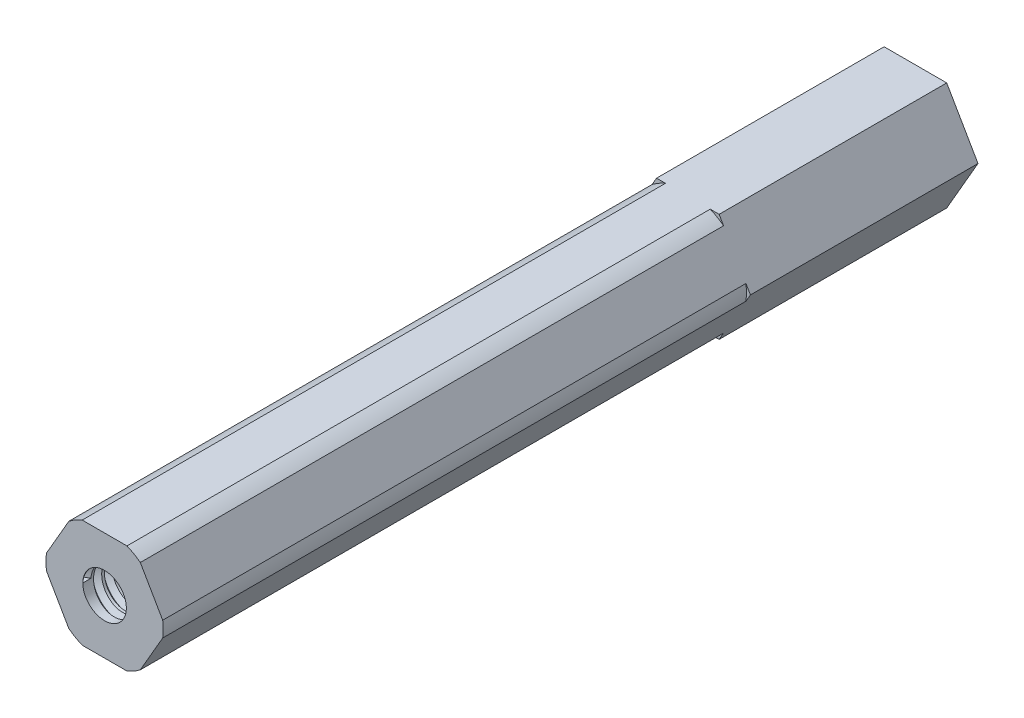
SolidWorks part; units mm, degrees
material "7075-T6 (SN)"
ref_plane "Alzado" through (0, 0, 0) normal (0, 0, 1) x (1, 0, 0)
ref_plane "Planta" through (0, 0, 0) normal (0, 1, 0) x (1, 0, 0)
ref_plane "Vista lateral" through (0, 0, 0) normal (1, 0, 0) x (0, 0, -1)
sketch "Croquis2" plane through (0, 0, 0) normal (0, 0, 1) x (1, 0, 0)
  line L1 (3.6662, -6.35) -> (7.3323, 0)
  line L2 (7.3323, 0) -> (3.6662, 6.35)
  line L3 (3.6662, 6.35) -> (-3.6662, 6.35)
  line L4 (-3.6662, 6.35) -> (-7.3323, 0)
  line L5 (-7.3323, 0) -> (-3.6662, -6.35)
  line L6 (-3.6662, -6.35) -> (3.6662, -6.35)
  circle A0 centre (0, 0) radius 6.35 construction
  dimension "D1" = 12.7
extrude "Extrusión Hex Profile" add sketch "Croquis2" along normal mid plane 95.0214
sketch "Croquis3" plane through (0, 0, 0) normal (0, 0, 1) x (1, 0, 0)
  circle A0 centre (0, 0) radius 2.5527
  dimension "D1" = 5.1054
extrude "Tap Hole 1" cut sketch "Croquis3" against normal blind 19.05 from surface starting at face at (0, 0, 47.5107)
extrude "Tap Hole 2" cut sketch "Croquis3<3>" along normal blind 19.05 from surface starting at face at (0, 0, -47.5107)
sketch "Croquis3<3>" plane through (0, 0, 0) normal (0, 0, 1) x (1, 0, 0) same geometry as "Croquis3"
sketch "Croquis7" plane through (0, 0, 0) normal (0, 0, 1) x (1, 0, 0)
  circle A0 centre (0, 0) radius 6.8707
  dimension "D1" = 13.7414
extrude "ThunderHex" cut sketch "Croquis7" along normal through all and the other way offset from surface 26.67 flip side to cut other way up to face at (2.5527, 0, -47.5107)
sketch "Croquis8" plane through (0, 0, 0) normal (0, 1, 0) x (1, 0, 0)
  line L0 (0, -47.5107) -> (-5.5562, -47.5107) construction
  line L1 (2.6237, -47.5107) -> (-2.6237, -47.5107) construction
  line L3 (0, -47.5107) -> (0, 0) construction
  line L4 (-5.5562, -47.5107) -> (-6.35, -46.717)
  line L5 (-6.35, -46.717) -> (-6.35, -45.9232)
  line L6 (-6.35, -45.9232) -> (-5.9055, -45.9232)
  line L7 (-5.9055, -45.9232) -> (-5.9055, -44.3357)
  line L8 (-5.9055, -44.3357) -> (-12.7, -44.3357)
  line L9 (-12.7, -44.3357) -> (-12.7, -47.5107)
  line L10 (-12.7, -47.5107) -> (-5.5562, -47.5107)
  line L11 (-4.1874, -47.5107) -> (-6.8111, -47.5107) construction
  dimension "D1" = 11.811
  dimension "D2" = 12.7
  dimension "D3" = 45
  dimension "D4" = 0.7937
  dimension "D6" = 0.7937
  dimension "D7" = 3.175
  dimension "D8" = 25.4
revolve "Retaining Ring 1" [suppressed] cut sketch "Croquis8" angle 360 about L3
sketch "Croquis9" plane through (0, 0, 0) normal (0, -1, 0) x (1, 0, 0)
  line L0 (0, -47.5107) -> (-5.5562, -47.5107) construction
  line L3 (0, -47.5107) -> (0, 0) construction
  line L4 (-5.5562, -47.5107) -> (-6.35, -46.717)
  line L5 (-6.35, -46.717) -> (-6.35, -45.9232)
  line L6 (-6.35, -45.9232) -> (-5.9055, -45.9232)
  line L7 (-5.9055, -45.9232) -> (-5.9055, -44.3357)
  line L8 (-5.9055, -44.3357) -> (-12.7, -44.3357)
  line L9 (-12.7, -44.3357) -> (-12.7, -47.5107)
  line L10 (-12.7, -47.5107) -> (-5.5562, -47.5107)
  line L12 (-3.6662, -47.5107) -> (3.6662, -47.5107) construction
  line L13 (-7.3323, -47.5107) -> (-3.6662, -47.5107) construction
  dimension "D1" = 11.811
  dimension "D2" = 12.7
  dimension "D3" = 45
  dimension "D4" = 0.7937
  dimension "D6" = 0.7937
  dimension "D7" = 3.175
  dimension "D8" = 25.4
revolve "Retaining Ring 2" [suppressed] cut sketch "Croquis9" angle 360 about L3
sketch "Croquis10" plane through (0, 0, 0) normal (0, 1, 0) x (1, 0, 0)
  line L0 (0, -47.5107) -> (0, 0) construction
  line L1 (2.6237, -47.5107) -> (-2.6237, -47.5107) construction
  line L2 (0, -47.5107) -> (-5.5562, -47.5107) construction
  line L3 (-4.1874, -47.5107) -> (-6.8111, -47.5107) construction
  line L4 (-5.5562, -47.5107) -> (-6.35, -46.717)
  line L5 (-6.35, -46.717) -> (-6.35, -39.5605)
  line L6 (-6.35, -39.5605) -> (-9.525, -39.5605)
  line L7 (-9.525, -39.5605) -> (-9.525, -47.5107)
  line L8 (-9.525, -47.5107) -> (-5.5562, -47.5107)
  dimension "D2" = 12.7
  dimension "D1" = 45
  dimension "D3" = 0.7937
  dimension "D4" = 7.9502
  dimension "D5" = 19.05
revolve "Round End 1" [suppressed] cut sketch "Croquis10" angle 360 about L0
sketch "Croquis12" plane through (0, 0, 0) normal (0, -1, 0) x (1, 0, 0)
  line L0 (0, -47.5107) -> (0, 0) construction
  line L2 (0, -47.5107) -> (-5.5562, -47.5107) construction
  line L4 (-5.5562, -47.5107) -> (-6.35, -46.717)
  line L5 (-6.35, -46.717) -> (-6.35, -39.5605)
  line L6 (-6.35, -39.5605) -> (-9.525, -39.5605)
  line L7 (-9.525, -39.5605) -> (-9.525, -47.5107)
  line L8 (-9.525, -47.5107) -> (-5.5562, -47.5107)
  line L9 (-3.6662, -47.5107) -> (3.6662, -47.5107) construction
  dimension "D1" = 45
  dimension "D3" = 0.7937
  dimension "D4" = 7.9502
  dimension "D2" = 12.7
  dimension "D5" = 19.05
revolve "Round End 2" [suppressed] cut sketch "Croquis12" angle 360 about L0
thread "Rosca1" pitch 1.27 method cut profile "Perfil de rosca2" start angle 0, offset 0, length 0, pitch 1.27, diameter 5.1054
ref_plane "Plano2" through (-2.5527, 0, 47.5107) normal (0, -1, 0) x (-1, 0, 0)
sketch "Perfil de rosca2" plane through (-2.5527, 0, 47.5107) normal (0, -1, 0) x (-1, 0, 0)
  line L0 (0, 0) -> (0, 1.27) construction
  line L1 (0, 0) -> (0.6874, 0.3969)
  line L2 (0.6874, 0.3969) -> (0.6874, 0.5556)
  line L3 (0.6874, 0.5556) -> (0, 0.9525)
  line L4 (0.6874, 0.4762) -> (0, 0.4762) construction
  line L11 (0, 0) -> (0, 0.9525)
  point P2 (0, 0)
  dimension "Pitch" = 1.27
  dimension "Profile_Angle" = 60
  dimension "Profile_Land" = 0.1588
  dimension "Profile_Height" = 0.6874
thread "Rosca2" pitch 1.27 method cut profile "Perfil de rosca3" start angle 0, offset 0, length 0, pitch 1.27, diameter 5.1054
ref_plane "Plano3" through (2.5527, 0, -47.5107) normal (0, -1, 0) x (1, 0, 0)
sketch "Perfil de rosca3" plane through (2.5527, 0, -47.5107) normal (0, -1, 0) x (1, 0, 0)
  line L0 (0, 0) -> (0, 1.27) construction
  line L1 (0, 0) -> (0.6874, 0.3969)
  line L2 (0.6874, 0.3969) -> (0.6874, 0.5556)
  line L3 (0.6874, 0.5556) -> (0, 0.9525)
  line L4 (0.6874, 0.4762) -> (0, 0.4762) construction
  line L11 (0, 0) -> (0, 0.9525)
  point P2 (0, 0)
  dimension "Pitch" = 1.27
  dimension "Profile_Angle" = 60
  dimension "Profile_Land" = 0.1588
  dimension "Profile_Height" = 0.6874
equation "\"HexOD\"= 0.5pulgadas"
equation "\"Largo\"= 3.741pulgadas"
equation "\"D1@Croquis2\"=\"HexOD\""
equation "\"D1@Extrusión Hex Profile\" = \"Largo\""
equation "\"TapHole\"= IIF ( \"HexOD\" = 0.5pulgadas , 0.2010pulgadas , 0.190pulgadas )"
equation "\"D1@Croquis3\"=\"TapHole\""
equation "\"ProTapHole\"= 0.75pulgadas"
equation "\"D1@Tap Hole 1\" = \"ProTapHole\""
equation "\"D1@Tap Hole 2\" = \"ProTapHole\""
equation "\"ThunderHex\"= IIF ( \"HexOD\" = 0.5pulgadas , 0.541pulgadas , 0.4035pulgadas )"
equation "\"D1@Croquis7\"=\"ThunderHex\""
equation "\"D2@Croquis8\"=\"HexOD\""
equation "\"D1@Croquis8\"=if(\"HexOD\"=0.5pulgadas, 0.465pulgadas, 0.35pulgadas )"
equation "\"D2@Croquis9\"=\"HexOD\""
equation "\"D1@Croquis9\"=if(\"HexOD\"=0.5pulgadas, 0.465pulgadas, 0.35pulgadas )"
equation "\"D8@Croquis8\"=\"HexOD\"*2"
equation "\"D8@Croquis9\"=\"HexOD\"*2"
equation "\"D5@Croquis10\"=\"HexOD\"*1.5"
equation "\"D5@Croquis12\"=\"HexOD\"*1.5"
equation "\"D4@Croquis10\"=if( \"D2@Croquis10\"=<0.375, 0.28, 0.313)"
equation "\"D4@Croquis12\"=if( \"D2@Croquis10\"=<0.375, 0.28, 0.313)"
